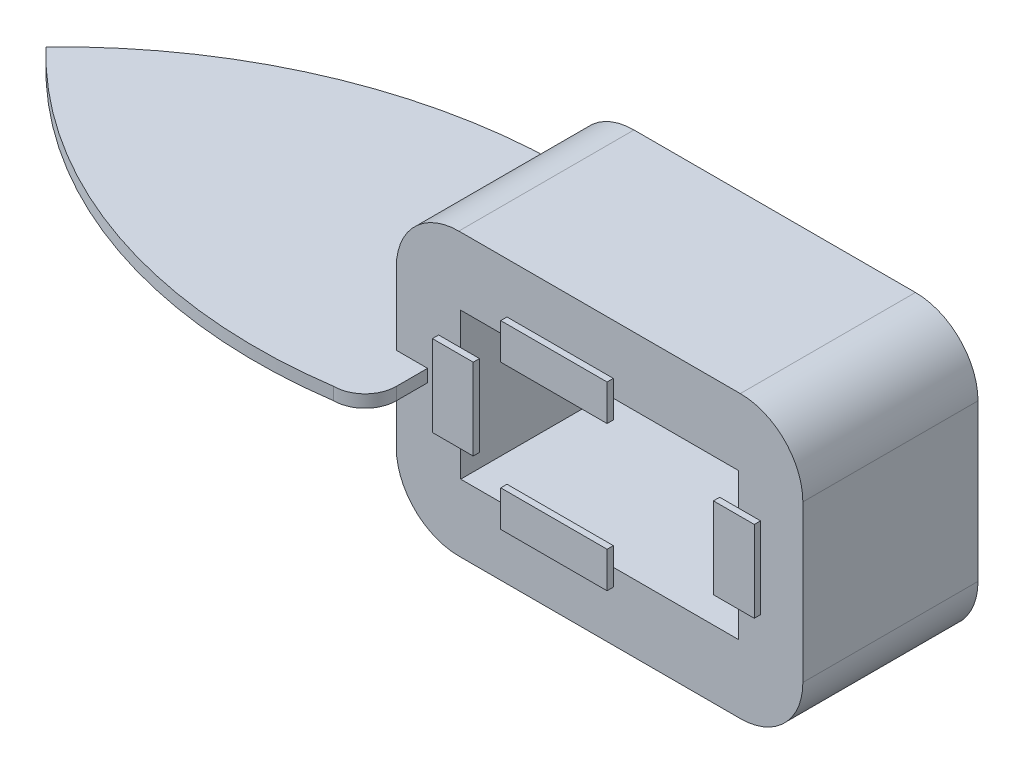
SolidWorks part; units mm, degrees
ref_plane "前基準面" through (0, 0, 0) normal (0, 0, 1) x (1, 0, 0)
ref_plane "上基準面" through (0, 0, 0) normal (0, 1, 0) x (1, 0, 0)
ref_plane "右基準面" through (0, 0, 0) normal (1, 0, 0) x (0, 0, -1)
sketch "草圖1" plane through (0, 0, 0) normal (0, 0, 1) x (1, 0, 0)
  line L0 (-9.02, 0) -> (7.9922, 0) construction
  line L2 (-59.9347, 22.5) -> (5.0653, 22.5)
  line L3 (-59.9347, 22.5) -> (-59.9347, -22.5)
  line L4 (-59.9347, -22.5) -> (5.0653, -22.5)
  line L5 (5.0653, 22.5) -> (5.0653, -22.5)
  dimension "D1" = 45
  dimension "D2" = 22.5
  dimension "D3" = 65
extrude "填料-伸長1" add sketch "草圖1" along normal blind 28
sketch "草圖2" plane through (0, 0, 0) normal (0, 0, 1) x (1, 0, 0)
  line L0 (-59.9347, 0) -> (5.361, 0) construction
  line L1 (-59.9347, 22.5) -> (-59.9347, -22.5) construction
  line L2 (-27.4347, 22.5) -> (-27.4347, -22.5) construction
  line L3 (5.0653, 22.5) -> (-59.9347, 22.5) construction
  line L4 (-59.9347, -22.5) -> (5.0653, -22.5) construction
  line L6 (-49.6347, 11.7) -> (-5.2347, 11.7)
  line L7 (-49.6347, 11.7) -> (-49.6347, -11.7)
  line L8 (-49.6347, -11.7) -> (-5.2347, -11.7)
  line L9 (-5.2347, 11.7) -> (-5.2347, -11.7)
  dimension "D1" = 44.4
  dimension "D2" = 23.4
  dimension "D3" = 10.3
  dimension "D4" = 10.8
extrude "除料-伸長1" cut sketch "草圖2" along normal blind 39
ref_plane "平面1" through (0, 0, 28) normal (0, 0, 1) x (1, 0, 0)
sketch "草圖3" plane through (0, 0, 28) normal (0, 0, 1) x (1, 0, 0)
  line L0 (-59.9347, 22.5) -> (-59.9347, -22.5) construction
  line L2 (-59.9347, 12) -> (-55.9347, 12)
  line L3 (-59.9347, 12) -> (-59.9347, -12)
  line L4 (-59.9347, -12) -> (-55.9347, -12)
  line L5 (-55.9347, 12) -> (-55.9347, -12)
  line L8 (-5.2347, -11.7) -> (-49.6347, -11.7) construction
  dimension "D1" = 4
  dimension "D2" = 24
  dimension "D3" = 0.3
ref_plane "平面2" through (-59.9347, 0, 0) normal (-1, 0, 0) x (0, 0, 1)
sketch "草圖6" plane through (0, 0, 28) normal (0, 0, 1) x (1, 0, 0)
  line L0 (-15.2347, 0.3) -> (5.0653, -22.5)
  line L1 (-5.2347, 11.7) -> (-5.2347, -11.7) construction
  line L2 (-5.2347, -11.7) -> (-49.6347, -11.7) construction
  line L3 (-15.2347, 0.3) -> (-15.2347, -22.5)
  line L4 (-59.9347, -22.5) -> (5.0653, -22.5) construction
  line L5 (-15.2347, -22.5) -> (5.0653, -22.5)
  dimension "D1" = 10
  dimension "D2" = 12
ref_plane "平面4" through (0, 0, 0) normal (0, 0, -1) x (-1, 0, 0)
fillet "圓角1" radius 10 1 edges at (-59.9347, -22.5, 14) type face fillet first side face at (-59.9347, 0, 14) second side face at (-27.4347, -22.5, 14)
fillet "圓角2" radius 10 1 edges at (-59.9347, 22.5, 14) type face fillet first side face at (-27.4347, 22.5, 14) second side face at (-59.9347, 5, 14)
fillet "圓角3" radius 10 1 edges at (5.0653, 22.5, 14) type face fillet first side face at (-22.4347, 22.5, 14) second side face at (5.0653, 0, 14)
fillet "圓角4" radius 10 1 edges at (5.0653, -22.5, 14) type face fillet first side face at (-22.4347, -22.5, 14) second side face at (5.0653, -5, 14)
ref_plane "平面6" through (0, 0, 29) normal (0, 0, 1) x (1, 0, 0)
sketch "草圖10" plane through (0, 0, 29) normal (0, 0, 1) x (1, 0, 0)
  line L6 (-49.6347, 0) -> (-4.2092, 0) construction
  line L7 (-49.6347, -11.7) -> (-49.6347, 11.7) construction
  line L8 (-27.4347, -11.7) -> (-27.4347, 19.297) construction
  line L9 (-5.2347, -11.7) -> (-49.6347, -11.7) construction
  line L11 (-49.6347, 6.5) -> (-53.1651, 6.5)
  line L14 (-53.1651, 6.5) -> (-53.1651, -6.5)
  line L17 (-49.6347, 6.5) -> (-46.6347, 6.5)
  line L18 (-46.6347, 6.5) -> (-46.6347, -6.5)
  line L20 (-42.2347, -11.7) -> (-42.2347, -8.7)
  line L25 (-42.2347, -11.7) -> (-42.2347, -14.4546)
  line L27 (-8.2347, 6.5) -> (-8.2347, -6.5)
  line L28 (-8.2347, -6.5) -> (-5.2347, -6.5)
  line L29 (-5.2347, -6.5) -> (-1.7043, -6.5)
  line L30 (-1.7043, 6.5) -> (-1.7043, -6.5)
  line L32 (-25.2347, 8.7) -> (-25.2347, 14.4546)
  line L33 (-25.2347, -14.4546) -> (-25.2347, -8.7)
  line L34 (-25.2347, -14.4546) -> (-42.2347, -14.4546)
  line L35 (-25.2347, -8.7) -> (-42.2347, -8.7)
  line L36 (-25.2347, 8.7) -> (-42.2347, 8.7)
  line L37 (-25.2347, 14.4546) -> (-42.2347, 14.4546)
  line L38 (-42.2347, 8.7) -> (-42.2347, 14.4546)
  line L39 (-46.6347, -6.5) -> (-53.1651, -6.5)
  line L40 (-1.7043, 6.5) -> (-8.2347, 6.5)
  dimension "D3" = 13
  dimension "D4" = 6.5
extrude "填料-伸長6" add sketch "草圖10" against normal blind 1 separate body
sketch "草圖19" plane through (0, 0, 0) normal (0, 1, 0) x (1, 0, 0)
  line L0 (-59.9347, 6.325) -> (-59.9347, -6.325) construction
  line L1 (-59.9347, 1.0971) -> (-54.9347, 1.0971)
  line L2 (-59.9347, 1.0971) -> (-59.9347, -29)
  line L3 (-59.9347, -29) -> (-54.9347, -29)
  line L4 (-54.9347, 1.0971) -> (-54.9347, -29)
  line L5 (-24.75, -29) -> (24.75, -29) construction
  dimension "D1" = 5
ref_plane "平面7" through (0, 0, 28) normal (0, 0, 1) x (1, 0, 0)
sketch "草圖20" plane through (0, 0, 28) normal (0, 0, 1) x (1, 0, 0)
  line L0 (-59.9347, 12.5) -> (-59.9347, -12.5) construction
  line L1 (-59.9347, 1) -> (-54.932, 1)
  line L2 (-59.9347, 1) -> (-59.9347, -1)
  line L3 (-59.9347, -1) -> (-54.932, -1)
  line L4 (-54.932, 1) -> (-54.932, -1)
  line L5 (-59.9347, 0) -> (-54.9347, 0) construction
  dimension "D1" = 5.0026
  dimension "D2" = 2
  dimension "D3" = 1
extrude "填料-伸長7" add sketch "草圖20" along normal blind 10
ref_plane "平面8" through (0, 0, 0) normal (0, 0, -1) x (-1, 0, 0)
sketch "草圖21" plane through (0, 0, 0) normal (0, 0, -1) x (-1, 0, 0)
  line L0 (59.9347, 0) -> (54.9347, 0) construction
  line L1 (54.9323, 1) -> (59.9347, 1)
  line L2 (54.9323, 1) -> (54.9323, -1)
  line L3 (54.9323, -1) -> (59.9347, -1)
  line L4 (59.9347, 1) -> (59.9347, -1)
  dimension "D1" = 5.0023
  dimension "D2" = 2
  dimension "D3" = 1
extrude "填料-伸長8" add sketch "草圖21" along normal blind 10
sketch "草圖22" plane through (0, 0, 0) normal (0, 1, 0) x (1, 0, 0)
  line L1 (-59.9347, 10) -> (-59.9347, -38)
  line L2 (-59.9347, -14) -> (-129.9347, -14) construction
  arc A2 (-129.9347, -14) -> (-59.9347, 10) centre (-71.5653, -70.1606) cw
  arc A3 (-129.9347, -14) -> (-59.9347, -38) centre (-71.5653, 42.1606) ccw
  dimension "D2" = 81
  dimension "D3" = 81
  dimension "D4" = 48
  dimension "D1" = 70
extrude "填料-伸長9" add sketch "草圖22" along normal blind 1 and the other way blind 1
fillet "圓角5" radius 5 1 edges at (-54.9323, 0, -10) type face fillet first side face at (-57.4335, 0, -10) second side face at (-54.9323, 0, -5)
fillet "圓角6" radius 5 1 edges at (-54.932, 0, 38) type face fillet first side face at (-57.4333, 0, 38) second side face at (-54.932, 0, 33)
